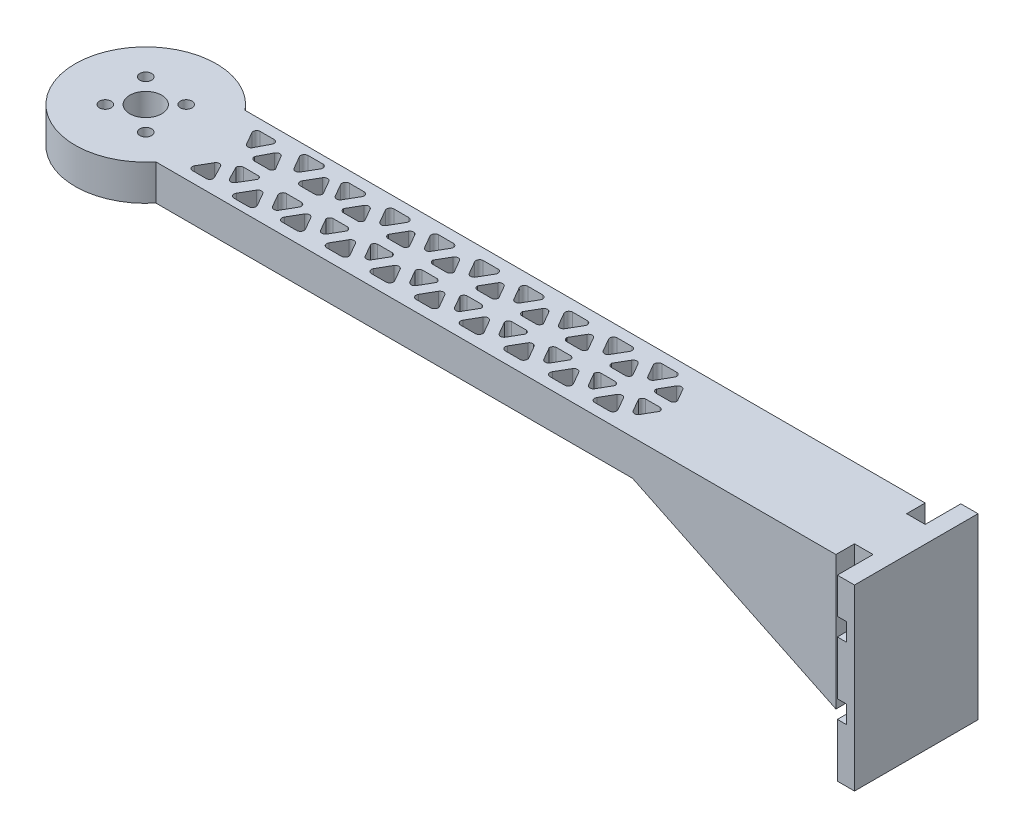
SolidWorks part; units mm, degrees
note: The reader was unsure of these and kept them because the rebuilt part matched: shared geometry of "Sketch2<4>".
ref_plane "Front Plane" through (0, 0, 0) normal (0, 0, 1) x (1, 0, 0)
ref_plane "Top Plane" through (0, 0, 0) normal (0, 1, 0) x (1, 0, 0)
ref_plane "Right Plane" through (0, 0, 0) normal (1, 0, 0) x (0, 0, -1)
sketch "Sketch1" plane through (0, 0, 0) normal (0, 1, 0) x (1, 0, 0)
  line L0 (19.7015, -0.0803) -> (215.7812, -0.0803) construction
  line L1 (15.2517, 12.4197) -> (215.7812, 12.4197)
  line L2 (15.2517, -12.5803) -> (215.7812, -12.5803)
  line L3 (215.7812, 12.4197) -> (215.7812, -12.5803)
  line L4 (22.4549, 9.4197) -> (26.384, 9.4197)
  line L5 (27.2449, 8.0014) -> (25.383, 4.4231)
  line L6 (23.682, 4.3855) -> (21.6147, 7.9638)
  line L7 (29.7182, 6.2554) -> (27.8031, 2.5747)
  line L8 (33.7755, 2.3958) -> (31.5736, 6.0947)
  line L9 (28.7602, 1.4197) -> (33.171, 1.4197)
  line L10 (37.9612, 5.1841) -> (40.0285, 8.7624)
  line L11 (34.1207, 8.7624) -> (36.188, 5.1841)
  line L12 (39.1419, 10.2986) -> (35.0073, 10.2986)
  line L13 (45.3949, 1.819) -> (41.2604, 1.819)
  line L14 (40.3733, 3.3543) -> (42.441, 6.9413)
  line L15 (44.2142, 6.9413) -> (46.2815, 3.363)
  line L16 (47.5213, 9.3393) -> (51.6558, 9.3393)
  line L17 (52.5425, 7.8032) -> (50.4752, 4.2249)
  line L18 (48.702, 4.2249) -> (46.6347, 7.8032)
  line L19 (54.955, 5.982) -> (52.8877, 2.4037)
  line L20 (58.7955, 2.3958) -> (56.7282, 5.982)
  line L21 (53.7743, 1.3393) -> (57.9089, 1.3393)
  line L22 (60.0313, 9.3393) -> (64.1658, 9.3393)
  line L23 (65.0525, 7.8032) -> (62.9852, 4.2249)
  line L24 (61.212, 4.2249) -> (59.1447, 7.8032)
  line L25 (67.465, 5.982) -> (65.3977, 2.4037)
  line L26 (71.3055, 2.3958) -> (69.2382, 5.982)
  line L27 (66.2843, 1.3393) -> (70.4189, 1.3393)
  line L28 (72.5413, 9.3393) -> (76.6758, 9.3393)
  line L29 (77.5625, 7.8032) -> (75.4952, 4.2249)
  line L30 (73.722, 4.2249) -> (71.6547, 7.8032)
  line L31 (79.975, 5.982) -> (77.9077, 2.4037)
  line L32 (83.8155, 2.3958) -> (81.7482, 5.982)
  line L33 (78.7943, 1.3393) -> (82.9289, 1.3393)
  line L34 (85.0513, 9.3393) -> (89.1858, 9.3393)
  line L35 (90.0725, 7.8032) -> (88.0052, 4.2249)
  line L36 (86.232, 4.2249) -> (84.1647, 7.8032)
  line L37 (92.485, 5.982) -> (90.4177, 2.4037)
  line L38 (96.3255, 2.3958) -> (94.2582, 5.982)
  line L39 (91.3043, 1.3393) -> (95.4389, 1.3393)
  line L40 (91.3043, -1.5) -> (95.4389, -1.5)
  line L41 (96.3255, -2.5565) -> (94.2582, -6.1427)
  line L42 (92.485, -6.1427) -> (90.4177, -2.5644)
  line L43 (86.232, -4.3855) -> (84.1647, -7.9638)
  line L44 (90.0725, -7.9638) -> (88.0052, -4.3855)
  line L45 (85.0513, -9.5) -> (89.1858, -9.5)
  line L46 (78.7943, -1.5) -> (82.9289, -1.5)
  line L47 (83.8155, -2.5565) -> (81.7482, -6.1427)
  line L48 (79.975, -6.1427) -> (77.9077, -2.5644)
  line L49 (73.722, -4.3855) -> (71.6547, -7.9638)
  line L50 (77.5625, -7.9638) -> (75.4952, -4.3855)
  line L51 (72.5413, -9.5) -> (76.6758, -9.5)
  line L52 (66.2843, -1.5) -> (70.4189, -1.5)
  line L53 (71.3055, -2.5565) -> (69.2382, -6.1427)
  line L54 (67.465, -6.1427) -> (65.3977, -2.5644)
  line L55 (61.212, -4.3855) -> (59.1447, -7.9638)
  line L56 (65.0525, -7.9638) -> (62.9852, -4.3855)
  line L57 (60.0313, -9.5) -> (64.1658, -9.5)
  line L58 (53.7743, -1.5) -> (57.9089, -1.5)
  line L59 (58.7955, -2.5565) -> (56.7282, -6.1427)
  line L60 (54.955, -6.1427) -> (52.8877, -2.5644)
  line L61 (48.702, -4.3855) -> (46.6347, -7.9638)
  line L62 (52.5425, -7.9638) -> (50.4752, -4.3855)
  line L63 (47.5213, -9.5) -> (51.6558, -9.5)
  line L64 (44.2142, -7.1019) -> (46.2815, -3.5236)
  line L65 (40.3733, -3.5149) -> (42.441, -7.1019)
  line L66 (45.3949, -1.9796) -> (41.2604, -1.9796)
  line L67 (39.1419, -10.4593) -> (35.0073, -10.4593)
  line L68 (34.1207, -8.9231) -> (36.188, -5.3448)
  line L69 (37.9612, -5.3448) -> (40.0285, -8.9231)
  line L70 (28.7602, -1.5803) -> (33.171, -1.5803)
  line L71 (33.7755, -2.5565) -> (31.5736, -6.2554)
  line L72 (29.7182, -6.4161) -> (27.8031, -2.7354)
  line L73 (23.682, -4.5462) -> (21.6147, -8.1245)
  line L74 (27.2449, -8.1621) -> (25.383, -4.5837)
  line L75 (22.4549, -9.5803) -> (26.384, -9.5803)
  line L76 (-0.0803, -16.7095) -> (-0.0803, 16.5488) construction
  line L77 (11.7312, -11.8919) -> (-11.8919, 11.7312) construction
  line L78 (-12.5321, -12.5321) -> (12.3715, 12.3715) construction
  line L79 (97.5613, 9.3393) -> (101.6958, 9.3393)
  line L80 (102.5825, 7.8032) -> (100.5152, 4.2249)
  line L81 (98.742, 4.2249) -> (96.6747, 7.8032)
  line L82 (104.995, 5.982) -> (102.9277, 2.4037)
  line L83 (108.8355, 2.3958) -> (106.7682, 5.982)
  line L84 (103.8143, 1.3393) -> (107.9489, 1.3393)
  line L85 (110.0713, 9.3393) -> (114.2058, 9.3393)
  line L86 (115.0925, 7.8032) -> (113.0252, 4.2249)
  line L87 (111.252, 4.2249) -> (109.1847, 7.8032)
  line L88 (117.505, 5.982) -> (115.4377, 2.4037)
  line L89 (121.3455, 2.3958) -> (119.2782, 5.982)
  line L90 (116.3243, 1.3393) -> (120.4589, 1.3393)
  line L91 (122.5813, 9.3393) -> (126.7158, 9.3393)
  line L92 (127.6025, 7.8032) -> (125.5352, 4.2249)
  line L93 (123.762, 4.2249) -> (121.6947, 7.8032)
  line L94 (130.015, 5.982) -> (127.9477, 2.4037)
  line L95 (133.8555, 2.3958) -> (131.7882, 5.982)
  line L96 (128.8343, 1.3393) -> (132.9689, 1.3393)
  line L97 (135.0913, 9.3393) -> (139.2258, 9.3393)
  line L98 (140.1125, 7.8032) -> (138.0452, 4.2249)
  line L99 (136.272, 4.2249) -> (134.2047, 7.8032)
  line L100 (142.525, 5.982) -> (140.4577, 2.4037)
  line L101 (146.3655, 2.3958) -> (144.2982, 5.982)
  line L102 (141.3443, 1.3393) -> (145.4789, 1.3393)
  line L139 (141.3443, -1.5) -> (145.4789, -1.5)
  line L140 (146.3655, -2.5565) -> (144.2982, -6.1427)
  line L141 (142.525, -6.1427) -> (140.4577, -2.5644)
  line L142 (136.272, -4.3855) -> (134.2047, -7.9638)
  line L143 (140.1125, -7.9638) -> (138.0452, -4.3855)
  line L144 (135.0913, -9.5) -> (139.2258, -9.5)
  line L145 (128.8343, -1.5) -> (132.9689, -1.5)
  line L146 (133.8555, -2.5565) -> (131.7882, -6.1427)
  line L147 (130.015, -6.1427) -> (127.9477, -2.5644)
  line L148 (123.762, -4.3855) -> (121.6947, -7.9638)
  line L149 (127.6025, -7.9638) -> (125.5352, -4.3855)
  line L150 (122.5813, -9.5) -> (126.7158, -9.5)
  line L151 (116.3243, -1.5) -> (120.4589, -1.5)
  line L152 (121.3455, -2.5565) -> (119.2782, -6.1427)
  line L153 (117.505, -6.1427) -> (115.4377, -2.5644)
  line L154 (111.252, -4.3855) -> (109.1847, -7.9638)
  line L155 (115.0925, -7.9638) -> (113.0252, -4.3855)
  line L156 (110.0713, -9.5) -> (114.2058, -9.5)
  line L157 (103.8143, -1.5) -> (107.9489, -1.5)
  line L158 (108.8355, -2.5565) -> (106.7682, -6.1427)
  line L159 (104.995, -6.1427) -> (102.9277, -2.5644)
  line L160 (98.742, -4.3855) -> (96.6747, -7.9638)
  line L161 (102.5825, -7.9638) -> (100.5152, -4.3855)
  line L162 (97.5613, -9.5) -> (101.6958, -9.5)
  line L163 (147.6013, 9.3393) -> (151.7358, 9.3393) [skipped]
  line L164 (152.6225, 7.8032) -> (150.5552, 4.2249) [skipped]
  line L165 (148.782, 4.2249) -> (146.7147, 7.8032) [skipped]
  line L166 (155.035, 5.982) -> (152.9677, 2.4037) [skipped]
  line L167 (158.8755, 2.3958) -> (156.8082, 5.982) [skipped]
  line L168 (153.8543, 1.3393) -> (157.9889, 1.3393) [skipped]
  line L169 (160.1113, 9.3393) -> (164.2458, 9.3393) [skipped]
  line L170 (165.1325, 7.8032) -> (163.0652, 4.2249) [skipped]
  line L171 (161.292, 4.2249) -> (159.2247, 7.8032) [skipped]
  line L172 (167.545, 5.982) -> (165.4777, 2.4037) [skipped]
  line L173 (171.3855, 2.3958) -> (169.3182, 5.982) [skipped]
  line L174 (166.3643, 1.3393) -> (170.4989, 1.3393) [skipped]
  line L175 (172.6213, 9.3393) -> (176.7558, 9.3393) [skipped]
  line L176 (177.6425, 7.8032) -> (175.5752, 4.2249) [skipped]
  line L177 (173.802, 4.2249) -> (171.7347, 7.8032) [skipped]
  line L178 (180.055, 5.982) -> (177.9877, 2.4037) [skipped]
  line L179 (183.8955, 2.3958) -> (181.8282, 5.982) [skipped]
  line L180 (178.8743, 1.3393) -> (183.0089, 1.3393) [skipped]
  circle A0 centre (-0.0803, -0.0803) radius 19.7818
  arc A1 (25.383, 4.4231) -> (23.682, 4.3855) centre (24.5222, 4.871) cw
  arc A2 (22.4549, 9.4197) -> (21.6147, 7.9638) centre (22.4549, 8.4493) ccw
  arc A3 (26.384, 9.4197) -> (27.2449, 8.0014) centre (26.384, 8.4493) cw
  arc A4 (33.171, 1.4197) -> (33.7755, 2.3958) centre (32.7524, 2.3541) ccw
  arc A5 (31.5736, 6.0947) -> (29.7182, 6.2554) centre (30.6092, 5.7508) ccw
  arc A6 (28.7602, 1.4197) -> (27.8031, 2.5747) centre (28.8569, 2.4738) cw
  arc A7 (35.0073, 10.2986) -> (34.1207, 8.7624) centre (35.0073, 9.2747) ccw
  arc A8 (39.1419, 10.2986) -> (40.0285, 8.7624) centre (39.1419, 9.2747) cw
  arc A9 (36.188, 5.1841) -> (37.9612, 5.1841) centre (37.0746, 5.6963) ccw
  arc A10 (45.3949, 1.819) -> (46.2815, 3.363) centre (45.3995, 2.8429) ccw
  arc A11 (42.441, 6.9413) -> (44.2142, 6.9413) centre (43.3276, 6.4291) cw
  arc A12 (41.2604, 1.819) -> (40.3733, 3.3543) centre (41.2604, 2.8429) cw
  arc A13 (50.4752, 4.2249) -> (48.702, 4.2249) centre (49.5886, 4.7371) cw
  arc A14 (47.5213, 9.3393) -> (46.6347, 7.8032) centre (47.5213, 8.3154) ccw
  arc A15 (51.6558, 9.3393) -> (52.5425, 7.8032) centre (51.6558, 8.3154) cw
  arc A16 (57.9089, 1.3393) -> (58.7955, 2.3958) centre (57.7724, 2.3541) ccw
  arc A17 (56.7282, 5.982) -> (54.955, 5.982) centre (55.8416, 5.4698) ccw
  arc A18 (53.7743, 1.3393) -> (52.8877, 2.4037) centre (53.9105, 2.3542) cw
  arc A19 (62.9852, 4.2249) -> (61.212, 4.2249) centre (62.0986, 4.7371) cw
  arc A20 (60.0313, 9.3393) -> (59.1447, 7.8032) centre (60.0313, 8.3154) ccw
  arc A21 (64.1658, 9.3393) -> (65.0525, 7.8032) centre (64.1658, 8.3154) cw
  arc A22 (70.4189, 1.3393) -> (71.3055, 2.3958) centre (70.2824, 2.3541) ccw
  arc A23 (69.2382, 5.982) -> (67.465, 5.982) centre (68.3516, 5.4698) ccw
  arc A24 (66.2843, 1.3393) -> (65.3977, 2.4037) centre (66.4205, 2.3542) cw
  arc A25 (75.4952, 4.2249) -> (73.722, 4.2249) centre (74.6086, 4.7371) cw
  arc A26 (72.5413, 9.3393) -> (71.6547, 7.8032) centre (72.5413, 8.3154) ccw
  arc A27 (76.6758, 9.3393) -> (77.5625, 7.8032) centre (76.6758, 8.3154) cw
  arc A28 (82.9289, 1.3393) -> (83.8155, 2.3958) centre (82.7924, 2.3541) ccw
  arc A29 (81.7482, 5.982) -> (79.975, 5.982) centre (80.8616, 5.4698) ccw
  arc A30 (78.7943, 1.3393) -> (77.9077, 2.4037) centre (78.9305, 2.3542) cw
  arc A31 (88.0052, 4.2249) -> (86.232, 4.2249) centre (87.1186, 4.7371) cw
  arc A32 (85.0513, 9.3393) -> (84.1647, 7.8032) centre (85.0513, 8.3154) ccw
  arc A33 (89.1858, 9.3393) -> (90.0725, 7.8032) centre (89.1858, 8.3154) cw
  arc A34 (95.4389, 1.3393) -> (96.3255, 2.3958) centre (95.3024, 2.3541) ccw
  arc A35 (94.2582, 5.982) -> (92.485, 5.982) centre (93.3716, 5.4698) ccw
  arc A36 (91.3043, 1.3393) -> (90.4177, 2.4037) centre (91.4405, 2.3542) cw
  arc A37 (91.3043, -1.5) -> (90.4177, -2.5644) centre (91.4405, -2.5148) ccw
  arc A38 (94.2582, -6.1427) -> (92.485, -6.1427) centre (93.3716, -5.6305) cw
  arc A39 (95.4389, -1.5) -> (96.3255, -2.5565) centre (95.3024, -2.5148) cw
  arc A40 (89.1858, -9.5) -> (90.0725, -7.9638) centre (89.1858, -8.4761) ccw
  arc A41 (85.0513, -9.5) -> (84.1647, -7.9638) centre (85.0513, -8.4761) cw
  arc A42 (88.0052, -4.3855) -> (86.232, -4.3855) centre (87.1186, -4.8978) ccw
  arc A43 (78.7943, -1.5) -> (77.9077, -2.5644) centre (78.9305, -2.5148) ccw
  arc A44 (81.7482, -6.1427) -> (79.975, -6.1427) centre (80.8616, -5.6305) cw
  arc A45 (82.9289, -1.5) -> (83.8155, -2.5565) centre (82.7924, -2.5148) cw
  arc A46 (76.6758, -9.5) -> (77.5625, -7.9638) centre (76.6758, -8.4761) ccw
  arc A47 (72.5413, -9.5) -> (71.6547, -7.9638) centre (72.5413, -8.4761) cw
  arc A48 (75.4952, -4.3855) -> (73.722, -4.3855) centre (74.6086, -4.8978) ccw
  arc A49 (66.2843, -1.5) -> (65.3977, -2.5644) centre (66.4205, -2.5148) ccw
  arc A50 (69.2382, -6.1427) -> (67.465, -6.1427) centre (68.3516, -5.6305) cw
  arc A51 (70.4189, -1.5) -> (71.3055, -2.5565) centre (70.2824, -2.5148) cw
  arc A52 (64.1658, -9.5) -> (65.0525, -7.9638) centre (64.1658, -8.4761) ccw
  arc A53 (60.0313, -9.5) -> (59.1447, -7.9638) centre (60.0313, -8.4761) cw
  arc A54 (62.9852, -4.3855) -> (61.212, -4.3855) centre (62.0986, -4.8978) ccw
  arc A55 (53.7743, -1.5) -> (52.8877, -2.5644) centre (53.9105, -2.5148) ccw
  arc A56 (56.7282, -6.1427) -> (54.955, -6.1427) centre (55.8416, -5.6305) cw
  arc A57 (57.9089, -1.5) -> (58.7955, -2.5565) centre (57.7724, -2.5148) cw
  arc A58 (51.6558, -9.5) -> (52.5425, -7.9638) centre (51.6558, -8.4761) ccw
  arc A59 (47.5213, -9.5) -> (46.6347, -7.9638) centre (47.5213, -8.4761) cw
  arc A60 (50.4752, -4.3855) -> (48.702, -4.3855) centre (49.5886, -4.8978) ccw
  arc A61 (41.2604, -1.9796) -> (40.3733, -3.5149) centre (41.2604, -3.0036) ccw
  arc A62 (42.441, -7.1019) -> (44.2142, -7.1019) centre (43.3276, -6.5897) ccw
  arc A63 (45.3949, -1.9796) -> (46.2815, -3.5236) centre (45.3995, -3.0036) cw
  arc A64 (36.188, -5.3448) -> (37.9612, -5.3448) centre (37.0746, -5.857) cw
  arc A65 (39.1419, -10.4593) -> (40.0285, -8.9231) centre (39.1419, -9.4353) ccw
  arc A66 (35.0073, -10.4593) -> (34.1207, -8.9231) centre (35.0073, -9.4353) cw
  arc A67 (28.7602, -1.5803) -> (27.8031, -2.7354) centre (28.8569, -2.6345) ccw
  arc A68 (31.5736, -6.2554) -> (29.7182, -6.4161) centre (30.6092, -5.9115) cw
  arc A69 (33.171, -1.5803) -> (33.7755, -2.5565) centre (32.7524, -2.5148) cw
  arc A70 (26.384, -9.5803) -> (27.2449, -8.1621) centre (26.384, -8.61) ccw
  arc A71 (22.4549, -9.5803) -> (21.6147, -8.1245) centre (22.4549, -8.61) cw
  arc A72 (25.383, -4.5837) -> (23.682, -4.5462) centre (24.5222, -5.0316) ccw
  circle A73 centre (-6.7979, 6.6372) radius 1.65
  circle A74 centre (5.5765, 5.5765) radius 1.65
  circle A75 centre (6.6372, -6.7979) radius 1.65
  circle A76 centre (-5.7372, -5.7372) radius 1.65
  circle A77 centre (-0.0803, -0.0803) radius 4.5
  arc A78 (100.5152, 4.2249) -> (98.742, 4.2249) centre (99.6286, 4.7371) cw
  arc A79 (97.5613, 9.3393) -> (96.6747, 7.8032) centre (97.5613, 8.3154) ccw
  arc A80 (101.6958, 9.3393) -> (102.5825, 7.8032) centre (101.6958, 8.3154) cw
  arc A81 (107.9489, 1.3393) -> (108.8355, 2.3958) centre (107.8124, 2.3541) ccw
  arc A82 (106.7682, 5.982) -> (104.995, 5.982) centre (105.8816, 5.4698) ccw
  arc A83 (103.8143, 1.3393) -> (102.9277, 2.4037) centre (103.9505, 2.3542) cw
  arc A84 (113.0252, 4.2249) -> (111.252, 4.2249) centre (112.1386, 4.7371) cw
  arc A85 (110.0713, 9.3393) -> (109.1847, 7.8032) centre (110.0713, 8.3154) ccw
  arc A86 (114.2058, 9.3393) -> (115.0925, 7.8032) centre (114.2058, 8.3154) cw
  arc A87 (120.4589, 1.3393) -> (121.3455, 2.3958) centre (120.3224, 2.3541) ccw
  arc A88 (119.2782, 5.982) -> (117.505, 5.982) centre (118.3916, 5.4698) ccw
  arc A89 (116.3243, 1.3393) -> (115.4377, 2.4037) centre (116.4605, 2.3542) cw
  arc A90 (125.5352, 4.2249) -> (123.762, 4.2249) centre (124.6486, 4.7371) cw
  arc A91 (122.5813, 9.3393) -> (121.6947, 7.8032) centre (122.5813, 8.3154) ccw
  arc A92 (126.7158, 9.3393) -> (127.6025, 7.8032) centre (126.7158, 8.3154) cw
  arc A93 (132.9689, 1.3393) -> (133.8555, 2.3958) centre (132.8324, 2.3541) ccw
  arc A94 (131.7882, 5.982) -> (130.015, 5.982) centre (130.9016, 5.4698) ccw
  arc A95 (128.8343, 1.3393) -> (127.9477, 2.4037) centre (128.9705, 2.3542) cw
  arc A96 (138.0452, 4.2249) -> (136.272, 4.2249) centre (137.1586, 4.7371) cw
  arc A97 (135.0913, 9.3393) -> (134.2047, 7.8032) centre (135.0913, 8.3154) ccw
  arc A98 (139.2258, 9.3393) -> (140.1125, 7.8032) centre (139.2258, 8.3154) cw
  arc A99 (145.4789, 1.3393) -> (146.3655, 2.3958) centre (145.3424, 2.3541) ccw
  arc A100 (144.2982, 5.982) -> (142.525, 5.982) centre (143.4116, 5.4698) ccw
  arc A101 (141.3443, 1.3393) -> (140.4577, 2.4037) centre (141.4805, 2.3542) cw
  arc A138 (141.3443, -1.5) -> (140.4577, -2.5644) centre (141.4805, -2.5148) ccw
  arc A139 (144.2982, -6.1427) -> (142.525, -6.1427) centre (143.4116, -5.6305) cw
  arc A140 (145.4789, -1.5) -> (146.3655, -2.5565) centre (145.3424, -2.5148) cw
  arc A141 (139.2258, -9.5) -> (140.1125, -7.9638) centre (139.2258, -8.4761) ccw
  arc A142 (135.0913, -9.5) -> (134.2047, -7.9638) centre (135.0913, -8.4761) cw
  arc A143 (138.0452, -4.3855) -> (136.272, -4.3855) centre (137.1586, -4.8978) ccw
  arc A144 (128.8343, -1.5) -> (127.9477, -2.5644) centre (128.9705, -2.5148) ccw
  arc A145 (131.7882, -6.1427) -> (130.015, -6.1427) centre (130.9016, -5.6305) cw
  arc A146 (132.9689, -1.5) -> (133.8555, -2.5565) centre (132.8324, -2.5148) cw
  arc A147 (126.7158, -9.5) -> (127.6025, -7.9638) centre (126.7158, -8.4761) ccw
  arc A148 (122.5813, -9.5) -> (121.6947, -7.9638) centre (122.5813, -8.4761) cw
  arc A149 (125.5352, -4.3855) -> (123.762, -4.3855) centre (124.6486, -4.8978) ccw
  arc A150 (116.3243, -1.5) -> (115.4377, -2.5644) centre (116.4605, -2.5148) ccw
  arc A151 (119.2782, -6.1427) -> (117.505, -6.1427) centre (118.3916, -5.6305) cw
  arc A152 (120.4589, -1.5) -> (121.3455, -2.5565) centre (120.3224, -2.5148) cw
  arc A153 (114.2058, -9.5) -> (115.0925, -7.9638) centre (114.2058, -8.4761) ccw
  arc A154 (110.0713, -9.5) -> (109.1847, -7.9638) centre (110.0713, -8.4761) cw
  arc A155 (113.0252, -4.3855) -> (111.252, -4.3855) centre (112.1386, -4.8978) ccw
  arc A156 (103.8143, -1.5) -> (102.9277, -2.5644) centre (103.9505, -2.5148) ccw
  arc A157 (106.7682, -6.1427) -> (104.995, -6.1427) centre (105.8816, -5.6305) cw
  arc A158 (107.9489, -1.5) -> (108.8355, -2.5565) centre (107.8124, -2.5148) cw
  arc A159 (101.6958, -9.5) -> (102.5825, -7.9638) centre (101.6958, -8.4761) ccw
  arc A160 (97.5613, -9.5) -> (96.6747, -7.9638) centre (97.5613, -8.4761) cw
  arc A161 (100.5152, -4.3855) -> (98.742, -4.3855) centre (99.6286, -4.8978) ccw
  arc A162 (150.5552, 4.2249) -> (148.782, 4.2249) centre (149.6686, 4.7371) cw [skipped]
  arc A163 (147.6013, 9.3393) -> (146.7147, 7.8032) centre (147.6013, 8.3154) ccw [skipped]
  arc A164 (151.7358, 9.3393) -> (152.6225, 7.8032) centre (151.7358, 8.3154) cw [skipped]
  arc A165 (157.9889, 1.3393) -> (158.8755, 2.3958) centre (157.8524, 2.3541) ccw [skipped]
  arc A166 (156.8082, 5.982) -> (155.035, 5.982) centre (155.9216, 5.4698) ccw [skipped]
  arc A167 (153.8543, 1.3393) -> (152.9677, 2.4037) centre (153.9905, 2.3542) cw [skipped]
  arc A168 (163.0652, 4.2249) -> (161.292, 4.2249) centre (162.1786, 4.7371) cw [skipped]
  arc A169 (160.1113, 9.3393) -> (159.2247, 7.8032) centre (160.1113, 8.3154) ccw [skipped]
  arc A170 (164.2458, 9.3393) -> (165.1325, 7.8032) centre (164.2458, 8.3154) cw [skipped]
  arc A171 (170.4989, 1.3393) -> (171.3855, 2.3958) centre (170.3624, 2.3541) ccw [skipped]
  arc A172 (169.3182, 5.982) -> (167.545, 5.982) centre (168.4316, 5.4698) ccw [skipped]
  arc A173 (166.3643, 1.3393) -> (165.4777, 2.4037) centre (166.5005, 2.3542) cw [skipped]
  arc A174 (175.5752, 4.2249) -> (173.802, 4.2249) centre (174.6886, 4.7371) cw [skipped]
  arc A175 (172.6213, 9.3393) -> (171.7347, 7.8032) centre (172.6213, 8.3154) ccw [skipped]
  arc A176 (176.7558, 9.3393) -> (177.6425, 7.8032) centre (176.7558, 8.3154) cw [skipped]
  arc A177 (183.0089, 1.3393) -> (183.8955, 2.3958) centre (182.8724, 2.3541) ccw [skipped]
  arc A178 (181.8282, 5.982) -> (180.055, 5.982) centre (180.9416, 5.4698) ccw [skipped]
  arc A179 (178.8743, 1.3393) -> (177.9877, 2.4037) centre (179.0105, 2.3542) cw [skipped]
  point P5 (-0.0803, -0.0803)
  point P8 (-0.0803, -0.0803)
  point P55 (30.6092, 5.7508)
  point P66 (37.0746, 5.6963)
  point P74 (43.3276, 6.4291)
  point P93 (55.8416, 5.4698)
  point P112 (68.3516, 5.4698)
  point P131 (80.8616, 5.4698)
  point P150 (93.3716, 5.4698)
  point P239 (93.3716, -5.6305)
  point P240 (80.8616, -5.6305)
  point P241 (68.3516, -5.6305)
  point P242 (55.8416, -5.6305)
  point P243 (43.3276, -6.5897)
  point P244 (37.0746, -5.857)
  point P245 (30.6092, -5.9115)
  point P247 (-0.0803, -0.0803)
  point P256 (180.9416, 5.4698)
  point P257 (168.4316, 5.4698)
  point P276 (105.8816, 5.4698)
  point P295 (118.3916, 5.4698)
  point P314 (130.9016, 5.4698)
  point P333 (143.4116, 5.4698)
  point P334 (155.9216, 5.4698)
  point P518 (143.4116, -5.6305)
  point P519 (130.9016, -5.6305)
  point P520 (118.3916, -5.6305)
  point P521 (105.8816, -5.6305)
  dimension "D7" = 3.3
  dimension "D8" = 3.3
  dimension "D9" = 3.3
  dimension "D10" = 3.3
  dimension "D15" = 9
  dimension "D1" = 3
  dimension "D2" = 3
  dimension "D3" = 25
  dimension "D4" = 3
  dimension "D5" = 45
  dimension "D6" = 90
  dimension "D11" = 9.5
  dimension "D12" = 9.5
  dimension "D13" = 8
  dimension "D14" = 8
  dimension "D16" = 8
extrude "Boss-Extrude1" add sketch "Sketch1" along normal blind 10
sketch "Sketch2" plane through (0, 10, 0) normal (0, 1, 0) x (1, 0, 0)
  line L0 (215.7812, 12.4197) -> (215.7812, 17.2197)
  line L1 (215.7812, 17.2197) -> (210.9812, 17.2197)
  line L2 (210.9812, 17.2197) -> (210.9812, -12.5803)
  line L3 (15.2517, -12.5803) -> (215.7812, -12.5803) construction
  line L4 (210.9812, -12.5803) -> (210.9812, -17.3803)
  line L5 (210.9812, -17.3803) -> (215.7812, -17.3803)
  line L6 (215.7812, -17.3803) -> (215.7812, -12.5803)
  line L7 (215.7812, -12.5803) -> (215.7812, 12.4197)
  line L8 (210.9812, -12.5803) -> (205.7812, -12.5803)
  line L17 (205.7812, -12.5803) -> (205.7812, -7.3803)
  line L18 (205.7812, -7.3803) -> (210.9812, -7.3803)
  line L19 (205.7812, 12.4197) -> (205.7812, 7.2197)
  line L20 (15.2517, 12.4197) -> (215.7812, 12.4197) construction
  line L21 (205.7812, 7.2197) -> (210.9812, 7.2197)
  line L22 (205.7812, 12.4197) -> (210.9812, 12.4197)
  line L23 (210.9812, 12.4197) -> (210.9812, 7.2197)
  line L24 (210.9812, -7.3803) -> (210.9812, -12.5803)
  dimension "D1" = 4.8
  dimension "D2" = 4.8
  dimension "D3" = 5.2
  dimension "D4" = 5.2
  dimension "D5" = 5.2
  dimension "D6" = 4.8
extrude "Boss-Extrude2" add sketch "Sketch2" against normal blind 50 contours L6 L7 L0 L1 L2 L4 L5
sketch "Sketch3" plane through (0, 0, 12.5803) normal (0, 0, 1) x (1, 0, 0)
  line L8 (210.9812, 0) -> (148.7812, 0)
  line L9 (15.2517, 0) -> (210.9812, 0) construction
  line L10 (210.9812, 0) -> (210.9812, -30)
  line L11 (210.9812, -40) -> (210.9812, 10) construction
  line L12 (210.9812, -30) -> (148.7812, 0)
extrude "Boss-Extrude3" add sketch "Sketch3" against normal up to surface (25 mm away) up to face at (113.1165, 5, -12.4197)
extrude "Cut-Extrude1" cut sketch "Sketch2<4>" against normal up to surface (40 mm away) contours L22 L19 L21 L2 | L18 L17 L8 L2
sketch "Sketch2<4>" plane through (0, 10, 0) normal (0, 1, 0) x (1, 0, 0) same geometry as "Sketch2"
sketch "Sketch4" plane through (0, 0, 17.3803) normal (0, 0, 1) x (1, 0, 0)
  line L0 (210.9812, -30) -> (210.9812, 10) construction
  line L1 (208.4812, -5) -> (213.4812, -5)
  line L2 (208.4812, -5) -> (208.4812, 0)
  line L3 (208.4812, 0) -> (213.4812, 0)
  line L4 (213.4812, -5) -> (213.4812, 0)
  line L5 (208.4812, -5) -> (213.4812, 0) construction
  line L6 (208.4812, 0) -> (213.4812, -5) construction
  line L7 (208.4812, 0) -> (208.4812, -5)
  line L8 (208.4812, -25) -> (213.4812, -25)
  line L9 (208.4812, -25) -> (208.4812, -20)
  line L10 (208.4812, -20) -> (213.4812, -20)
  line L11 (213.4812, -25) -> (213.4812, -20)
  line L12 (208.4812, -25) -> (213.4812, -20) construction
  line L13 (208.4812, -20) -> (213.4812, -25) construction
  line L14 (208.4812, 0) -> (208.3812, 0)
  line L15 (208.4812, -5) -> (208.3812, -5)
  line L16 (208.3812, 0) -> (208.3812, -5)
  line L17 (208.3812, -20) -> (208.3812, -25)
  line L18 (208.4812, -25) -> (208.3812, -25)
  line L19 (208.4812, -20) -> (208.3812, -20)
  line L20 (208.4812, -25) -> (208.4812, -20)
  line L21 (208.4812, -20) -> (208.4812, -25)
  point P0 (210.9812, -2.5)
  point P7 (210.9812, -22.5)
  line M7 (210.9812, 10) -> (210.9812, -40)
  dimension "D1" = 5
  dimension "D2" = 5
  dimension "D3" = 5
  dimension "D4" = 5
  dimension "D5" = 10
  dimension "D6" = 15
  dimension "D7" = 0.1
extrude "Cut-Extrude2" cut sketch "Sketch4" against normal up to surface (34.6 mm away) contours L10 L9 L8 M7 | L8 L11 L10 M7 | L3 L2 L1 M7 | L1 L4 L3 M7 | L9 L19 L17 L18 | L14 L16 L15 L2 up to face at (213.3812, -15, -17.2197)
